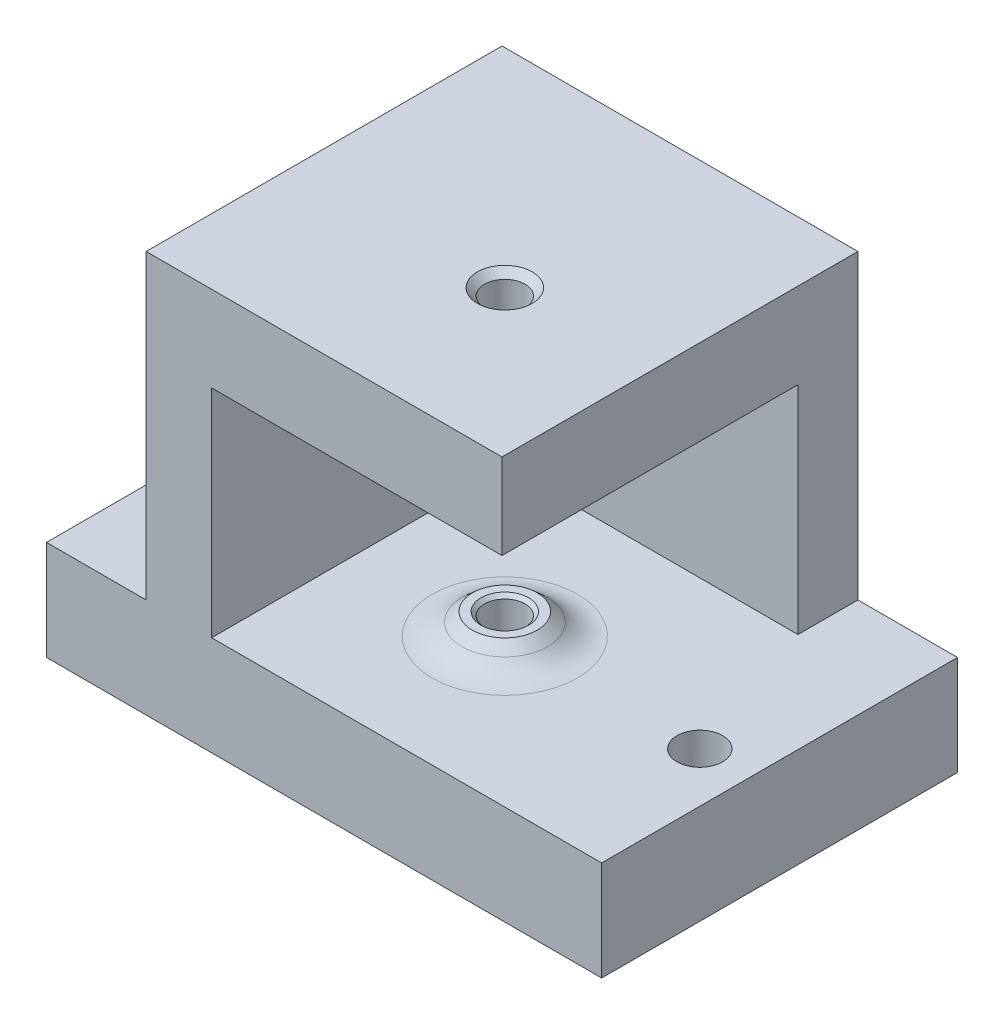
SolidWorks part; units mm, degrees
ref_plane "Front Plane" through (0, 0, 0) normal (0, 0, 1) x (1, 0, 0)
ref_plane "Top Plane" through (0, 0, 0) normal (0, 1, 0) x (1, 0, 0)
ref_plane "Right Plane" through (0, 0, 0) normal (1, 0, 0) x (0, 0, -1)
sketch "Sketch1" plane through (0, 0, 0) normal (0, 1, 0) x (1, 0, 0)
  line L1 (-12.5, -12.5) -> (12.5, -12.5)
  line L2 (-12.5, -12.5) -> (-12.5, 12.5)
  line L3 (-12.5, 12.5) -> (12.5, 12.5)
  line L4 (12.5, -12.5) -> (12.5, 12.5)
  line L5 (-12.5, -12.5) -> (12.5, 12.5) construction
  line L6 (-12.5, 12.5) -> (12.5, -12.5) construction
  point P0 (0, 0)
  dimension "D1" = 25
  dimension "D2" = 25
extrude "Boss-Extrude1" add sketch "Sketch1" along normal blind 7
sketch "Sketch2" plane through (0, 7, 0) normal (0, 1, 0) x (1, 0, 0)
  line L0 (-12.5, -12.5) -> (-7.8977, -12.5)
  line L1 (-12.5, -12.5) -> (12.5, -12.5) construction
  line L2 (-7.8977, -12.5) -> (-7.8977, 8.2913)
  line L3 (-7.8977, 8.2913) -> (12.5, 8.2913)
  line L4 (12.5, -12.5) -> (12.5, 12.5)
  line L5 (12.5, 12.5) -> (-12.5, 12.5)
  line L6 (-12.5, 12.5) -> (-12.5, -12.5)
  line L7 (-12.5, -12.5) -> (12.5, -12.5)
  line L9 (12.5, 12.5) -> (-12.5, 12.5)
  line L10 (-12.5, 12.5) -> (-12.5, -12.5)
  line L11 (12.5, -12.5) -> (12.5, 12.5) construction
  line L12 (12.5, 8.2913) -> (12.5, 12.5)
  dimension "D1" = 0
extrude "Boss-Extrude2" add sketch "Sketch2" along normal blind 15.2
sketch "Sketch3" plane through (0, 22.2, 0) normal (0, 1, 0) x (1, 0, 0)
  line L4 (12.5, -12.5) -> (12.5, 12.5)
  line L5 (-12.5, -12.5) -> (12.5, -12.5)
  line L6 (-12.5, 12.5) -> (-12.5, -12.5)
  line L7 (12.5, 12.5) -> (-12.5, 12.5)
  line L8 (12.5, -12.5) -> (12.5, 12.5)
  line L9 (-12.5, -12.5) -> (12.5, -12.5)
  line L10 (-12.5, 12.5) -> (-12.5, -12.5)
  line L11 (12.5, 12.5) -> (-12.5, 12.5)
  dimension "D1" = 0
extrude "Boss-Extrude3" add sketch "Sketch3" along normal blind 6
sketch "Sketch4" plane through (0, 7, 0) normal (0, 1, 0) x (1, 0, 0)
  line L0 (2.3012, 8.2913) -> (2.3012, -12.5) construction
  line L1 (-7.8977, -2.1044) -> (12.5, -2.1044) construction
  line L4 (12.5, 8.2913) -> (-7.8977, 8.2913)
  line L5 (-7.8977, 8.2913) -> (-7.8977, -12.5)
  line L6 (-7.8977, -12.5) -> (12.5, -12.5)
  line L7 (12.5, -12.5) -> (12.5, 8.2913)
  line L8 (12.5, 8.2913) -> (-7.8977, 8.2913) construction
  line L9 (-7.8977, 8.2913) -> (-7.8977, -12.5) construction
  line L10 (-7.8977, -12.5) -> (12.5, -12.5) construction
  line L11 (12.5, -12.5) -> (12.5, 8.2913) construction
  circle A0 centre (2.3012, -2.1044) radius 1.425
  dimension "D2" = 2.85
  dimension "D1" = 0
extrude "Cut-Extrude1" cut sketch "Sketch4" against normal through all both and the other way through all
sketch "Sketch5" plane through (0, 7, 0) normal (0, 1, 0) x (1, 0, 0)
  circle A0 centre (2.3012, -2.1044) radius 1.425
  circle A1 centre (2.3012, -2.1044) radius 2.5
  circle A2 centre (2.3012, -2.1044) radius 1.425 construction
  dimension "D1" = 5
extrude "Boss-Extrude4" add sketch "Sketch5" along normal blind 1.5
sketch "Sketch6" plane through (0, 22.2, 0) normal (0, -1, 0) x (1, 0, 0)
  circle A0 centre (2.3012, 2.1044) radius 1.425 construction
  circle A1 centre (2.3012, 2.1044) radius 1.425
  circle A2 centre (2.3012, 2.1044) radius 2.5
  dimension "D1" = 5
extrude "Boss-Extrude5" add sketch "Sketch6" along normal blind 1.5
fillet "Fillet1" radius 3 2 edges at (2.3012, 22.2, 4.6044) (2.3012, 7, -0.3956)
chamfer "Chamfer1" distance 1 angle 16 2 edges at (2.3012, 20.7, -0.3956) (2.3012, 8.5, 4.6044) first distance on face at (2.3012, 22.2, 7.2024) first distance on face at (2.3012, 7, -2.9937)
sketch "Sketch7" plane through (0, 20.7, 0) normal (0, -1, 0) x (1, 0, 0)
  circle A0 centre (2.3012, 2.1044) radius 1.425 construction
  circle A1 centre (2.3012, 2.1044) radius 1.425
  circle A2 centre (2.3012, 2.1044) radius 2.2751 construction
  circle A3 centre (2.3012, 2.1044) radius 2.2751
  point P5 (0, 0)
  dimension "D1" = 0.8501
chamfer "Chamfer2" distance 0.25 angle 45 2 edges at (2.3012, 8.5, 3.5294) (2.3012, 20.7, 0.6794)
chamfer "Chamfer3" distance 0.5 angle 45 2 edges at (2.3012, 28.2, 3.5294) (2.3012, 0, 3.5294)
sketch "Sketch8" plane through (0, 0, 0) normal (0, 1, 0) x (1, 0, 0)
  line L0 (2.3012, -2.1044) -> (17.6599, -2.1044) construction
  line L1 (12.5, 12.5) -> (19.5, 12.5)
  line L2 (19.5, 12.5) -> (19.5, -12.5)
  line L3 (19.5, -12.5) -> (12.5, -12.5)
  line L4 (12.5, -12.5) -> (12.5, 12.5)
  line L5 (0, 12.5) -> (0, -12.5) construction
  line L6 (12.5, 12.5) -> (-12.5, 12.5) construction
  line L7 (-12.5, -12.5) -> (12.5, -12.5) construction
  line L8 (-19.5, -12.5) -> (-12.5, -12.5)
  line L9 (-19.5, 12.5) -> (-19.5, -12.5)
  line L10 (-12.5, 12.5) -> (-19.5, 12.5)
  line L11 (-12.5, -12.5) -> (-12.5, 12.5)
  circle A0 centre (16, -2.1044) radius 1.6
  circle A1 centre (-16, -2.1044) radius 1.6
  point P13 (16, 12.5)
  dimension "D1" = 3.2
  dimension "D2" = 7
extrude "Boss-Extrude6" add sketch "Sketch8" along normal up to surface (7 mm away) up to face at (2.3012, 7, -2.9937)
